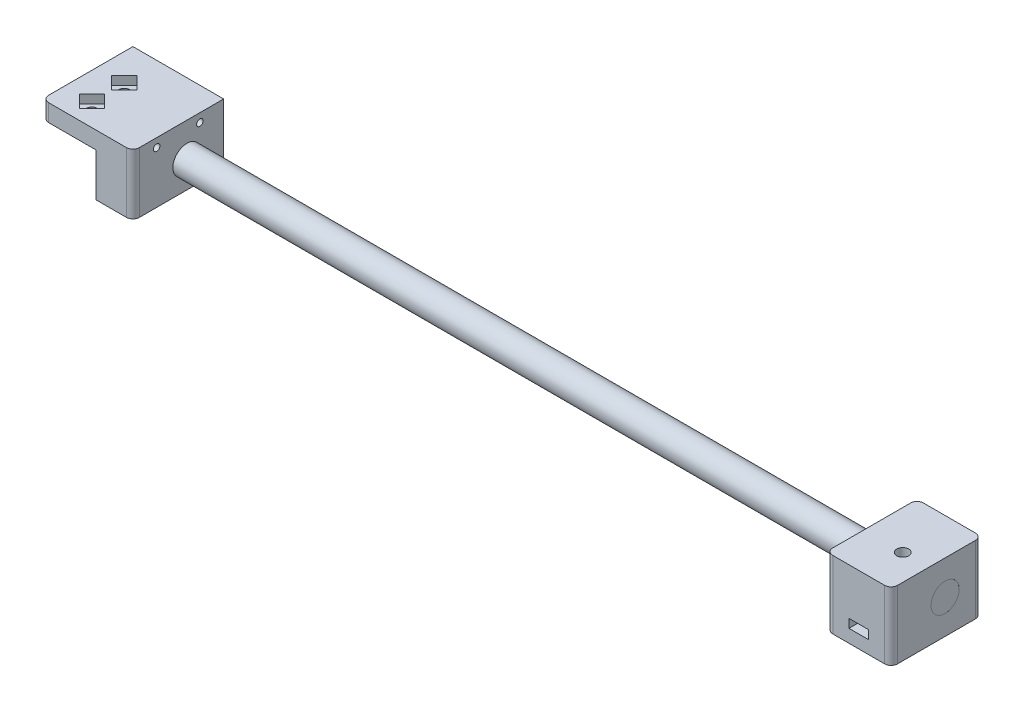
SolidWorks part; units mm, degrees
ref_plane "Front Plane" through (0, 0, 0) normal (0, 0, 1) x (1, 0, 0)
ref_plane "Top Plane" through (0, 0, 0) normal (0, 1, 0) x (1, 0, 0)
ref_plane "Right Plane" through (0, 0, 0) normal (1, 0, 0) x (0, 0, -1)
sketch "Sketch2" plane through (0, 0, 0) normal (0, 1, 0) x (1, 0, 0)
  line L1 (0, 0) -> (42, 0)
  line L2 (0, 0) -> (0, -42)
  line L3 (0, -42) -> (42, -42)
  line L4 (42, 0) -> (42, -42)
  dimension "D1" = 42
  dimension "D2" = 42
extrude "Boss-Extrude1" add sketch "Sketch2" against normal blind 22
sketch "Sketch3" plane through (0, 0, 0) normal (0, 1, 0) x (1, 0, 0)
  line L4 (0, 0) -> (0, -42)
  line L5 (0, -42) -> (42, -42)
  line L6 (42, -42) -> (42, 0)
  line L7 (42, 0) -> (0, 0)
  line L8 (0, 0) -> (0, -42)
  line L9 (0, -42) -> (42, -42)
  line L10 (42, -42) -> (42, 0)
  line L11 (42, 0) -> (0, 0)
  dimension "D1" = 0
extrude "Boss-Extrude2" add sketch "Sketch3" along normal blind 6
sketch "Sketch4" plane through (0, 0, 0) normal (-1, 0, 0) x (0, 0, 1)
  line L0 (0, -22) -> (42, -22) construction
  line L1 (42, -22) -> (42, 6) construction
  circle A0 centre (17, -9.8) radius 6.5
  dimension "D2" = 13
  dimension "D1" = 12.2
  dimension "D3" = 25
extrude "Boss-Extrude3" add sketch "Sketch4" against normal blind 368 from offset 25 separate body offset against normal yes
extrude "Cut-Extrude6" cut sketch "Sketch4<3>" against normal up to surface (42 mm away) from offset 25 up to face at (42, -8, 21) offset against normal yes
sketch "Sketch4<3>" plane through (0, 0, 0) normal (-1, 0, 0) x (0, 0, 1) same geometry as "Sketch4"
sketch "Sketch8" plane through (393, 0, 0) normal (1, 0, 0) x (0, 0, -1)
  line L0 (0, -22) -> (0, 6) construction
  line L1 (-42, -22) -> (-42, 6) construction
  line L2 (-42, -22) -> (0, -22) construction
  line L3 (0, -22) -> (0, 6)
  line L4 (-42, -22) -> (-42, 6)
  line L5 (-42, -22) -> (0, -22)
  line L6 (-42, 6) -> (0, 6)
  line L7 (-42, 6) -> (0, 6) construction
  circle A0 centre (-17, -9.8) radius 6.5 construction
  circle A1 centre (-17, -9.8) radius 6.5
extrude "Boss-Extrude5" add sketch "Sketch8" against normal blind 30 separate body
sketch "Sketch11" plane through (0, 0, 42) normal (0, 0, 1) x (1, 0, 0)
  line L1 (0, -22) -> (25, -22)
  line L2 (0, -22) -> (0, -2)
  line L3 (0, -2) -> (25, -2)
  line L4 (25, -22) -> (25, -2)
  dimension "D1" = 20
  dimension "D2" = 25
extrude "Cut-Extrude9" cut sketch "Sketch11" against normal blind 50
sketch "Sketch10" plane through (0, 6, 0) normal (0, 1, 0) x (1, 0, 0)
  line L0 (363, -24.6) -> (393, -24.6) construction
  line L3 (361, -24.6) -> (361, -37.1) construction
  line L4 (393, 0) -> (393, -42) construction
  line L5 (393, -21) -> (363, -21) construction
  line L6 (363, 0) -> (363, -42) construction
  circle A0 centre (381, -24.6) radius 11 construction
  circle A1 centre (361, -37.1) radius 11 construction
  circle A2 centre (361, -37.1) radius 2.75 construction
  circle A3 centre (381, -24.6) radius 2.75
  dimension "D1" = 22
  dimension "5.5" = 5.5
  dimension "D2" = 12.5
  dimension "D3" = 20
  dimension "D4" = 12
  dimension "D6" = 3.6
extrude "Cut-Extrude8" cut sketch "Sketch10" against normal blind 12
fillet "Fillet2" radius 3 4 edges at (363, -8, 42) (363, -8, 0) (393, -8, 0) (393, -8, 42)
fillet "Fillet1" radius 3 2 edges at (42, -8, 42) (0, 2, 42)
sketch "Sketch12" plane through (0, -2, 0) normal (0, -1, 0) x (1, 0, 0)
  line L0 (25, 42) -> (3, 42) construction
  line L1 (0, 0) -> (0, 39) construction
  circle A0 centre (12.5, 31.5) radius 2.5
  circle A1 centre (12.5, 16.5) radius 2.5
  dimension "D2" = 12.5
  dimension "D3" = 5
  dimension "D4" = 15
  dimension "D1" = 10.5
extrude "Cut-Extrude10" cut sketch "Sketch12" against normal blind 20
sketch "Sketch13" plane through (0, 6, 0) normal (0, 1, 0) x (1, 0, 0)
  line L1 (6.7017, -31.5) -> (12.5, -37.2983)
  line L2 (6.7017, -31.5) -> (12.5, -25.7017)
  line L3 (12.5, -25.7017) -> (18.2983, -31.5)
  line L4 (12.5, -37.2983) -> (18.2983, -31.5)
  line L5 (6.7017, -31.5) -> (18.2983, -31.5) construction
  line L6 (12.5, -25.7017) -> (12.5, -37.2983) construction
  line L7 (6.7017, -16.5) -> (12.5, -22.2983)
  line L8 (6.7017, -16.5) -> (12.5, -10.7017)
  line L9 (12.5, -10.7017) -> (18.2983, -16.5)
  line L10 (12.5, -22.2983) -> (18.2983, -16.5)
  line L11 (6.7017, -16.5) -> (18.2983, -16.5) construction
  line L12 (12.5, -10.7017) -> (12.5, -22.2983) construction
  point P0 (12.5, -31.5)
  point P6 (12.5, -16.5)
  dimension "D1" = 8.2
extrude "Cut-Extrude11" cut sketch "Sketch13" against normal blind 4
sketch "Sketch14" plane through (0, -22, 0) normal (0, -1, 0) x (1, 0, 0)
  line L0 (378, 42) -> (378, 0) construction
  line L1 (366, 42) -> (390, 42) construction
  line L2 (366, 0) -> (390, 0) construction
  circle A0 centre (378, 34) radius 2.5
  circle A1 centre (378, 16) radius 2.5
  dimension "D1" = 18
  dimension "D2" = 8
  dimension "D3" = 5
extrude "Cut-Extrude12" cut sketch "Sketch14" against normal blind 10
sketch "Sketch15" plane through (42, 0, 0) normal (1, 0, 0) x (0, 0, -1)
  line L0 (0, 2) -> (-42, 2) construction
  line L1 (0, 6) -> (0, -22) construction
  line L2 (-42, -22) -> (-42, 6) construction
  line L3 (0, 6) -> (-39, 6) construction
  line L4 (0, -2) -> (-39, -2) construction
  line L5 (-21, 2) -> (-21, 6) construction
  line L8 (-39, 6) -> (0, 6) construction
  circle A0 centre (-31, 2) radius 1.5
  circle A1 centre (-11, 2) radius 1.5
  dimension "D1" = 20
  dimension "D2" = 3
extrude "Cut-Extrude13" cut sketch "Sketch15" against normal blind 20
sketch "Sketch16" plane through (0, -22, 0) normal (0, -1, 0) x (1, 0, 0)
  line L4 (390, 42) -> (366, 42)
  line L5 (363, 39) -> (363, 3)
  line L6 (366, 0) -> (390, 0)
  line L7 (393, 3) -> (393, 39)
  line L8 (390, 42) -> (366, 42)
  line L9 (363, 39) -> (363, 3)
  line L10 (366, 0) -> (390, 0)
  line L11 (393, 3) -> (393, 39)
  circle A0 centre (378, 16) radius 2.5 construction
  circle A1 centre (378, 34) radius 2.5 construction
  circle A2 centre (378, 16) radius 2.5
  circle A3 centre (378, 34) radius 2.5
  arc A4 (366, 42) -> (363, 39) centre (366, 39) ccw
  arc A5 (363, 3) -> (366, 0) centre (366, 3) ccw
  arc A6 (390, 0) -> (393, 3) centre (390, 3) ccw
  arc A7 (393, 39) -> (390, 42) centre (390, 39) ccw
  arc A8 (366, 42) -> (363, 39) centre (366, 39) ccw
  arc A9 (363, 3) -> (366, 0) centre (366, 3) ccw
  arc A10 (390, 0) -> (393, 3) centre (390, 3) ccw
  arc A11 (393, 39) -> (390, 42) centre (390, 39) ccw
  dimension "D1" = 0
extrude "Boss-Extrude6" add sketch "Sketch16" along normal blind 3.5
sketch "Sketch18" plane through (0, -25.5, 0) normal (0, -1, 0) x (1, 0, 0)
  line L0 (373.5, 38.5) -> (373.5, 42)
  line L1 (373.5, 29.5) -> (382.5, 29.5)
  line L2 (373.5, 29.5) -> (373.5, 38.5)
  line L3 (373.5, 38.5) -> (382.5, 38.5) construction
  line L4 (382.5, 29.5) -> (382.5, 38.5)
  line L5 (373.5, 29.5) -> (382.5, 38.5) construction
  line L6 (373.5, 38.5) -> (382.5, 29.5) construction
  line L7 (373.5, 11.5) -> (382.5, 11.5)
  line L8 (373.5, 11.5) -> (373.5, 20.5)
  line L9 (373.5, 20.5) -> (382.5, 20.5)
  line L10 (382.5, 11.5) -> (382.5, 20.5)
  line L11 (373.5, 11.5) -> (382.5, 20.5) construction
  line L12 (373.5, 20.5) -> (382.5, 11.5) construction
  line L13 (390, 42) -> (366, 42) construction
  line L14 (373.5, 42) -> (382.5, 42)
  line L15 (382.5, 42) -> (382.5, 38.5)
  point P0 (378, 34)
  point P6 (378, 16)
  dimension "D1" = 9
extrude "Cut-Extrude14" cut sketch "Sketch18" against normal blind 4 from offset 6 offset against normal yes
sketch "Sketch19" plane through (0, -15.5, 0) normal (0, -1, 0) x (1, 0, 0)
  line L4 (382.5, 11.5) -> (382.5, 20.5)
  line L5 (373.5, 11.5) -> (382.5, 11.5)
  line L6 (373.5, 20.5) -> (373.5, 11.5)
  line L7 (382.5, 20.5) -> (373.5, 20.5)
  line L8 (382.5, 11.5) -> (382.5, 20.5)
  line L9 (373.5, 11.5) -> (382.5, 11.5)
  line L10 (373.5, 20.5) -> (373.5, 11.5)
  line L11 (382.5, 20.5) -> (373.5, 20.5)
  dimension "D1" = 0
extrude "Cut-Extrude15" cut sketch "Sketch19" against normal blind 7
sketch "Sketch20" plane through (0, -6, 0) normal (0, 1, 0) x (1, 0, 0)
  line L1 (376.5, -29.1) -> (385.5, -29.1)
  line L2 (376.5, -29.1) -> (376.5, -20.1)
  line L3 (376.5, -20.1) -> (385.5, -20.1)
  line L4 (385.5, -29.1) -> (385.5, -20.1)
  line L5 (376.5, -29.1) -> (385.5, -20.1) construction
  line L6 (376.5, -20.1) -> (385.5, -29.1) construction
  point P0 (381, -24.6)
  dimension "D1" = 9
extrude "Cut-Extrude16" cut sketch "Sketch20" along normal blind 7 and the other way blind 4
